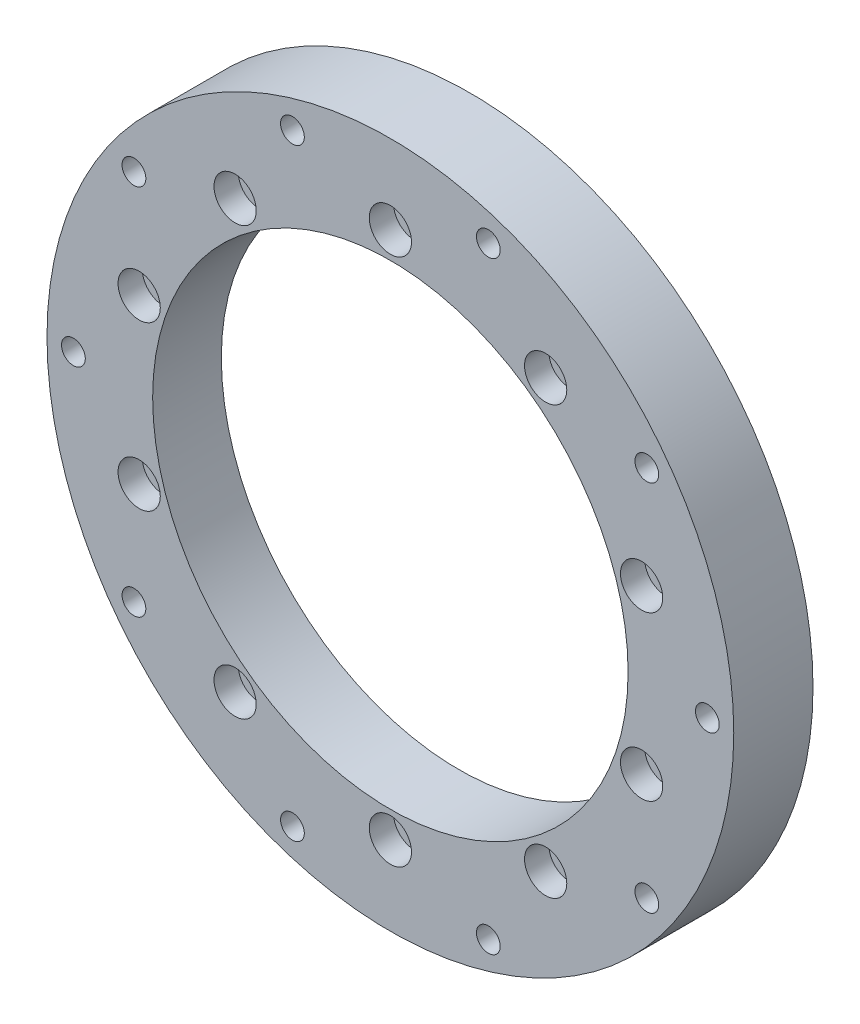
SolidWorks part; units mm, degrees
ref_plane "前视基准面" through (0, 0, 0) normal (0, 0, 1) x (1, 0, 0)
ref_plane "上视基准面" through (0, 0, 0) normal (0, 1, 0) x (1, 0, 0)
ref_plane "右视基准面" through (0, 0, 0) normal (1, 0, 0) x (0, 0, -1)
sketch "草图1" plane through (0, 0, 0) normal (0, 0, 1) x (1, 0, 0)
  circle A0 centre (0, 0) radius 65
  dimension "D1" = 130
extrude "凸台-拉伸1" add sketch "草图1" along normal blind 15
sketch "草图2" plane through (0, 0, 0) normal (0, 0, -1) x (-1, 0, 0)
  circle A0 centre (0, 0) radius 45
  dimension "D1" = 90
extrude "切除-拉伸1" cut sketch "草图2" against normal blind 15
sketch "草图3" plane through (0, 0, 0) normal (0, 0, -1) x (-1, 0, 0)
  circle A0 centre (0, 0) radius 53
  dimension "D1" = 106
extrude "切除-拉伸2" cut sketch "草图3" against normal blind 2
hole_wizard "打孔尺寸(%根据)内六角圆柱头螺钉的类型1" positions "草图5" profile "草图4" counterbore size "M4" standard "GB" end condition through all
sketch "草图5" plane through (0, 0, 15) normal (0, 0, 1) x (1, 0, 0)
  line L0 (0, 0) -> (0, 68.094) construction
  circle A0 centre (0, 0) radius 50 construction
  point P0 (0, 50)
  dimension "D1" = 100
sketch "草图4" plane through (0, 50, 15) normal (1, 0, 0) x (0, -1, 0)
  line L0 (0, 0) -> (0, 15)
  line L1 (0, 15) -> (2.25, 15)
  line L3 (2.25, 15) -> (2.25, 4.6)
  line L4 (2.25, 4.6) -> (4, 4.6)
  line L5 (4, 4.6) -> (4, 0)
  line L7 (4, 0) -> (0, 0)
  line L11 (0, -6.35) -> (0, 107.95) construction
  dimension "通孔孔直径" = 4.5
  dimension "通孔孔深度" = 15
  dimension "柱形沉头孔直径" = 8
  dimension "柱形沉头孔深度" = 4.6
ref_axis "基准轴1" through (0, 0, 15) along (0, 0, -1)
pattern_circular "阵列(圆周)1" count 10 over 360 about axis through (0, 0, 15) along (0, 0, -1) of "打孔尺寸(%根据)内六角圆柱头螺钉的类型1"
hole_wizard "打孔尺寸(%根据)内六角圆柱头螺钉的类型2" positions "草图7" profile "草图6" counterbore size "M4" standard "GB" end condition through all
sketch "草图7" plane through (0, 0, 0) normal (0, 0, -1) x (-1, 0, 0)
  line L0 (0, 0) -> (0, 68.749) construction
  line L2 (0, 0) -> (-23.4992, 72.3232) construction
  circle A0 centre (0, 0) radius 60 construction
  point P0 (-18.541, 57.0634)
  dimension "D1" = 120
  dimension "D2" = 18
sketch "草图6" plane through (18.541, 57.0634, 0) normal (1, 0, 0) x (0, 1, 0)
  line L0 (0, 0) -> (0, 15)
  line L1 (0, 15) -> (2.25, 15)
  line L3 (2.25, 15) -> (2.25, 4.6)
  line L4 (2.25, 4.6) -> (4, 4.6)
  line L5 (4, 4.6) -> (4, 0)
  line L7 (4, 0) -> (0, 0)
  line L11 (0, -6.35) -> (0, 107.95) construction
  dimension "通孔孔直径" = 4.5
  dimension "通孔孔深度" = 15
  dimension "柱形沉头孔直径" = 8
  dimension "柱形沉头孔深度" = 4.6
pattern_circular "阵列(圆周)2" count 10 over 360 about axis through (0, 0, 15) along (0, 0, -1) of "打孔尺寸(%根据)内六角圆柱头螺钉的类型2"
